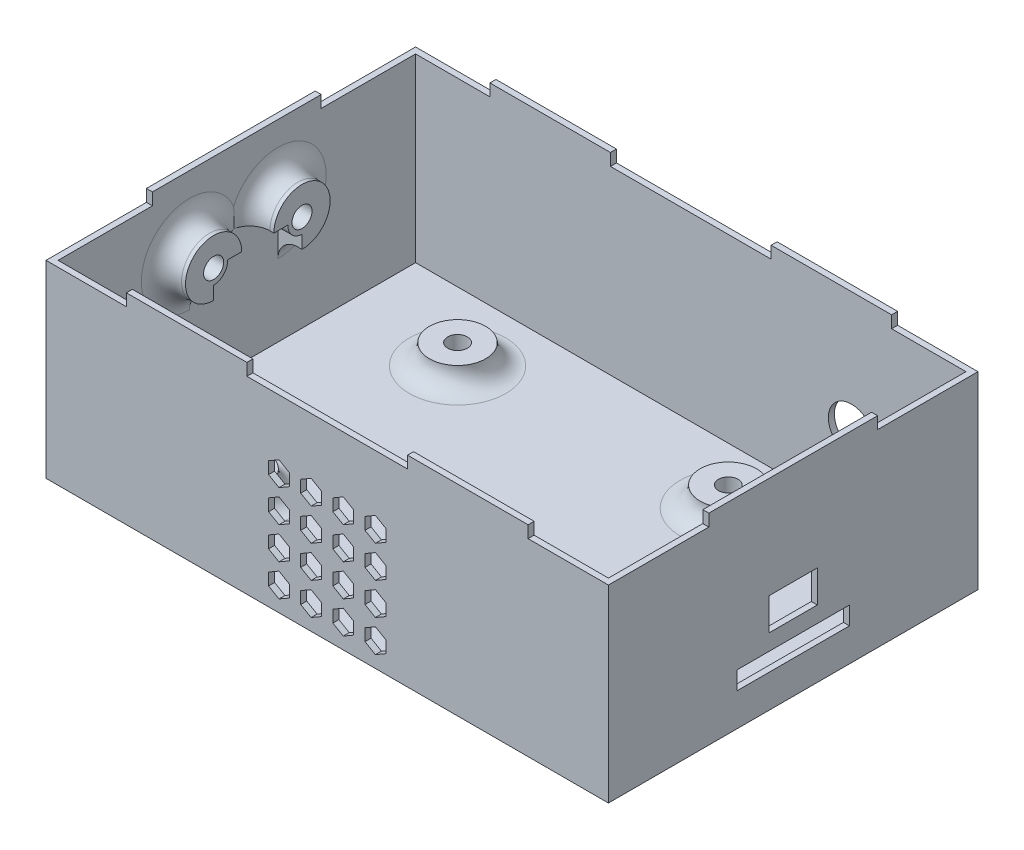
SolidWorks part; units mm, degrees
ref_plane "Front Plane" through (0, 0, 0) normal (0, 0, 1) x (1, 0, 0)
ref_plane "Top Plane" through (0, 0, 0) normal (0, 1, 0) x (1, 0, 0)
ref_plane "Right Plane" through (0, 0, 0) normal (1, 0, 0) x (0, 0, -1)
sketch "Sketch1" plane through (0, 0, 0) normal (0, 1, 0) x (1, 0, 0)
  line L1 (70, -46) -> (-70, -46)
  line L2 (70, -46) -> (70, 46)
  line L3 (70, 46) -> (-70, 46)
  line L4 (-70, -46) -> (-70, 46)
  line L5 (70, -46) -> (-70, 46) construction
  line L6 (70, 46) -> (-70, -46) construction
  line L12 (38, 12.25) -> (80, 12.25)
  line L13 (38, 12.25) -> (38, -12.25)
  line L14 (38, -12.25) -> (80, -12.25)
  line L15 (80, 12.25) -> (80, -12.25)
  line L16 (38, 12.25) -> (80, -12.25) construction
  line L17 (38, -12.25) -> (80, 12.25) construction
  line L22 (68.5, -44.5) -> (-68.5, -44.5)
  line L23 (68.5, -44.5) -> (68.5, 44.5)
  line L24 (68.5, 44.5) -> (-68.5, 44.5)
  line L25 (-68.5, -44.5) -> (-68.5, 44.5)
  line L26 (68.5, -44.5) -> (-68.5, 44.5) construction
  line L27 (68.5, 44.5) -> (-68.5, -44.5) construction
  circle A0 centre (-41.0549, 27.5) radius 7
  circle A1 centre (-41.0549, -27) radius 7
  circle A2 centre (23.3451, 30.5) radius 7
  circle A6 centre (40, -10.25) radius 3.5
  circle A7 centre (40, 10.25) radius 3.5
  point P0 (0, 0)
  point P6 (0, 0)
  point P9 (0, 0)
  point P22 (59, 0)
  dimension "D7" = 14
  dimension "D8" = 14
  dimension "D5" = 3
  dimension "D11" = 14
  dimension "D25" = 7
  dimension "D27" = 7
  dimension "D13" = 35.75
  dimension "D9" = 17
  dimension "D1" = 140
  dimension "D3" = 64.4
  dimension "D4" = 54.5
  dimension "D6" = 0
  dimension "D10" = 92
  dimension "D12" = 1.5
  dimension "D14" = 28.9451
  dimension "D19" = 30
  dimension "D20" = 20.5
  dimension "D21" = 10
  dimension "D23" = 2
  dimension "D24" = 1.5
  dimension "D26" = 2
  dimension "D28" = 2
  dimension "D29" = 30
extrude "Boss-Extrude2" add sketch "Sketch1" along normal blind 7 contours A2 | A0 | A1 | A6 | A7 region at (-41.0549, 0, -27.5) region at (-41.0549, 0, 27) region at (23.3451, 0, -30.5)
sketch "Sketch3" plane through (0, 0, 0) normal (0, 1, 0) x (1, 0, 0)
  line L1 (-70, -46) -> (70, -46)
  line L2 (-70, -46) -> (-70, 46)
  line L3 (-70, 46) -> (70, 46)
  line L4 (70, -46) -> (70, 46)
  line L5 (-70, -46) -> (70, 46) construction
  line L6 (-70, 46) -> (70, -46) construction
  point P0 (0, 0)
  dimension "D1" = 92
  dimension "D2" = 140
extrude "Boss-Extrude3" add sketch "Sketch3" along normal blind 2
sketch "Sketch4" plane through (0, 2, 0) normal (0, 1, 0) x (1, 0, 0)
  line L0 (70, 46) -> (-70, 46) construction
  line L1 (68.5, -44.5) -> (-68.5, -44.5)
  line L2 (68.5, -44.5) -> (68.5, 44.5)
  line L3 (68.5, 44.5) -> (-68.5, 44.5)
  line L4 (-68.5, -44.5) -> (-68.5, 44.5)
  line L5 (68.5, -44.5) -> (-68.5, 44.5) construction
  line L6 (68.5, 44.5) -> (-68.5, -44.5) construction
  line L7 (-70, 46) -> (-70, -46) construction
  line L9 (70, -46) -> (-70, -46)
  line L10 (70, -46) -> (70, 46)
  line L11 (70, 46) -> (-70, 46)
  line L12 (-70, -46) -> (-70, 46)
  line L13 (70, -46) -> (-70, 46) construction
  line L14 (70, 46) -> (-70, -46) construction
  point P0 (0, 0)
  point P10 (0, 0)
  dimension "D1" = 1.5
  dimension "D2" = 1.5
extrude "Boss-Extrude4" add sketch "Sketch4" along normal blind 45
sketch "Sketch5" plane through (0, 7, 0) normal (0, 1, 0) x (1, 0, 0)
  circle A0 centre (23.3451, 30.5) radius 2.45
  circle A1 centre (-41.0549, 27.5) radius 2.45
  circle A2 centre (-41.0549, -27) radius 2.45
  dimension "D1" = 4.9
  dimension "D4" = 4.9
  dimension "D5" = 4.9
extrude "Cut-Extrude1" cut sketch "Sketch5" against normal blind 5.1
sketch "Sketch6" plane through (0, 7, 0) normal (0, 1, 0) x (1, 0, 0)
  circle A0 centre (40, 10.25) radius 1
  circle A1 centre (40, -10.25) radius 1
  dimension "D1" = 2
  dimension "D2" = 2
extrude "Cut-Extrude2" cut sketch "Sketch6" against normal blind 5.1
sketch "Sketch7" plane through (-68.5, 0, 0) normal (1, 0, 0) x (0, 0, -1)
  line L0 (44.5, 2) -> (-44.5, 2) construction
  circle A0 centre (-11.7728, 32) radius 7
  circle A1 centre (10.2272, 32) radius 7
  dimension "D2" = 14
  dimension "D3" = 14
  dimension "D1" = 22
  dimension "D4" = 30
extrude "Boss-Extrude5" add sketch "Sketch7" along normal blind 6
sketch "Sketch8" plane through (-62.5, 0, 0) normal (1, 0, 0) x (0, 0, -1)
  circle A0 centre (-11.7728, 32) radius 2.5
  circle A1 centre (10.2272, 32) radius 2.5
  dimension "D1" = 5
  dimension "D2" = 5
extrude "Cut-Extrude3" cut sketch "Sketch8" against normal blind 5.1
sketch "Sketch9" plane through (0, 47, 0) normal (0, 1, 0) x (1, 0, 0)
  line L0 (-68.5, -44.5) -> (68.5, -44.5) construction
  line L1 (-50, -44.5) -> (-20, -44.5)
  line L2 (-50, -44.5) -> (-50, -46)
  line L3 (-50, -46) -> (-20, -46)
  line L4 (-20, -44.5) -> (-20, -46)
  line L5 (-70, -46) -> (70, -46) construction
  line L6 (-68.5, -44.5) -> (68.5, -44.5) construction
  line L7 (20, -44.5) -> (50, -44.5)
  line L8 (20, -44.5) -> (20, -46)
  line L9 (20, -46) -> (50, -46)
  line L10 (50, -44.5) -> (50, -46)
  line L11 (-70, 46) -> (-70, -46) construction
  line L12 (70, -46) -> (70, 46) construction
  line L13 (68.5, -44.5) -> (68.5, 44.5) construction
  line L18 (68.5, 21) -> (70, 21)
  line L19 (68.5, 21) -> (68.5, -21)
  line L20 (68.5, -21) -> (70, -21)
  line L21 (-68.5, 44.5) -> (-68.5, -44.5) construction
  line L22 (-68.5, -21) -> (-70, -21)
  line L23 (-68.5, -21) -> (-68.5, 21)
  line L24 (-68.5, 21) -> (-70, 21)
  line L25 (-70, -21) -> (-70, 21)
  line L26 (70, 46) -> (-70, 46) construction
  line L27 (70, 21) -> (70, -21)
  line L28 (68.5, 44.5) -> (-68.5, 44.5) construction
  line L29 (20, 44.5) -> (50, 44.5)
  line L30 (20, 44.5) -> (20, 46)
  line L31 (20, 46) -> (50, 46)
  line L32 (50, 44.5) -> (50, 46)
  line L34 (-50, 44.5) -> (-20, 44.5)
  line L35 (-50, 44.5) -> (-50, 46)
  line L36 (-50, 46) -> (-20, 46)
  line L37 (-20, 44.5) -> (-20, 46)
  dimension "D1" = 20
  dimension "D2" = 20
  dimension "D3" = 30
  dimension "D4" = 30
  dimension "D5" = 25
  dimension "D6" = 25
  dimension "D7" = 20
  dimension "D8" = 20
  dimension "D9" = 30
  dimension "D10" = 30
  dimension "D11" = 25
  dimension "D12" = 25
extrude "Boss-Extrude6" add sketch "Sketch9" along normal blind 3
sketch "Sketch11" plane through (70, 0, 0) normal (1, 0, 0) x (0, 0, -1)
  line L0 (-46, 0) -> (46, 0) construction
  line L1 (-14, 8.2) -> (14, 8.2)
  line L2 (-14, 8.2) -> (-14, 12.7)
  line L3 (-14, 12.7) -> (14, 12.7)
  line L4 (14, 8.2) -> (14, 12.7)
  line L5 (-46, 47) -> (-46, 0) construction
  line L7 (46, 47) -> (46, 0) construction
  dimension "D1" = 8.2
  dimension "D2" = 32
  dimension "D3" = 32
  dimension "D4" = 4.5
sketch "Sketch12" plane through (0, 7, 0) normal (0, 1, 0) x (1, 0, 0)
  circle A0 centre (40, 10.25) radius 3.5
  circle A1 centre (40, -10.25) radius 3.5
  circle A2 centre (40, 10.25) radius 1
  circle A3 centre (40, -10.25) radius 1
  dimension "D1" = 2
  dimension "D2" = 7
  dimension "D3" = 2
  dimension "D4" = 7
extrude "Boss-Extrude7" add sketch "Sketch12" along normal blind 2
extrude "Cut-Extrude4" cut sketch "Sketch11" against normal up to next
sketch "Sketch14" plane through (0, 0, -46) normal (0, 0, -1) x (-1, 0, 0)
  line L0 (-70, 47) -> (-70, 0) construction
  line L1 (-70, 0) -> (70, 0) construction
  circle A0 centre (-40, 20) radius 5.75
  dimension "D1" = 30
  dimension "D3" = 11.5
  dimension "D2" = 20
extrude "Cut-Extrude5" cut sketch "Sketch14" against normal up to next
sketch "Sketch15" plane through (0, 0, 46) normal (0, 0, 1) x (1, 0, 0)
  line L98 (-4.0006, 9) -> (-6.5987, 7.5)
  line L297 (-12.0019, 9) -> (-14.6, 7.5)
  line L299 (-14.6, 7.5) -> (-14.6, 4.5)
  line L301 (-14.6, 4.5) -> (-12.0019, 3)
  line L302 (-12.0019, 3) -> (-9.4038, 4.5)
  line L307 (-9.4038, 4.5) -> (-9.4038, 7.5)
  line L308 (-9.4038, 7.5) -> (-12.0019, 9)
  line L309 (-6.5987, 7.5) -> (-6.5987, 4.5)
  line L310 (-6.5987, 4.5) -> (-4.0006, 3)
  line L311 (-4.0006, 3) -> (-1.4026, 4.5)
  line L312 (-1.4026, 4.5) -> (-1.4026, 7.5)
  line L313 (-1.4026, 7.5) -> (-4.0006, 9)
  line L314 (4.0006, 9) -> (1.4026, 7.5)
  line L315 (1.4026, 7.5) -> (1.4026, 4.5)
  line L316 (1.4026, 4.5) -> (4.0006, 3)
  line L317 (4.0006, 3) -> (6.5987, 4.5)
  line L318 (6.5987, 4.5) -> (6.5987, 7.5)
  line L319 (6.5987, 7.5) -> (4.0006, 9)
  line L320 (12.0019, 9) -> (9.4038, 7.5)
  line L321 (9.4038, 7.5) -> (9.4038, 4.5)
  line L322 (9.4038, 4.5) -> (12.0019, 3)
  line L323 (12.0019, 3) -> (14.6, 4.5)
  line L324 (14.6, 4.5) -> (14.6, 7.5)
  line L325 (14.6, 7.5) -> (12.0019, 9)
  line L326 (-4.0006, 17) -> (-6.5987, 15.5)
  line L327 (-6.5987, 15.5) -> (-6.5987, 12.5)
  line L328 (-6.5987, 12.5) -> (-4.0006, 11)
  line L329 (-4.0006, 11) -> (-1.4026, 12.5)
  line L330 (-1.4026, 12.5) -> (-1.4026, 15.5)
  line L331 (-1.4026, 15.5) -> (-4.0006, 17)
  line L332 (4.0007, 17) -> (1.4026, 15.5)
  line L333 (1.4026, 15.5) -> (1.4026, 12.5)
  line L334 (1.4026, 12.5) -> (4.0007, 11)
  line L335 (4.0007, 11) -> (6.5987, 12.5)
  line L336 (6.5987, 12.5) -> (6.5987, 15.5)
  line L337 (6.5987, 15.5) -> (4.0007, 17)
  line L338 (12.0019, 17) -> (9.4039, 15.5)
  line L339 (9.4039, 15.5) -> (9.4039, 12.5)
  line L340 (9.4039, 12.5) -> (12.0019, 11)
  line L341 (12.0019, 11) -> (14.6, 12.5)
  line L342 (14.6, 12.5) -> (14.6, 15.5)
  line L343 (14.6, 15.5) -> (12.0019, 17)
  line L344 (-4.0006, 25) -> (-6.5987, 23.5)
  line L345 (-6.5987, 23.5) -> (-6.5987, 20.5)
  line L346 (-6.5987, 20.5) -> (-4.0006, 19)
  line L347 (-4.0006, 19) -> (-1.4025, 20.5)
  line L348 (-1.4025, 20.5) -> (-1.4025, 23.5)
  line L349 (-1.4025, 23.5) -> (-4.0006, 25)
  line L350 (4.0007, 25) -> (1.4026, 23.5)
  line L351 (1.4026, 23.5) -> (1.4026, 20.5)
  line L352 (1.4026, 20.5) -> (4.0007, 19)
  line L353 (4.0007, 19) -> (6.5987, 20.5)
  line L354 (6.5987, 20.5) -> (6.5987, 23.5)
  line L355 (6.5987, 23.5) -> (4.0007, 25)
  line L356 (12.0019, 25) -> (9.4039, 23.5)
  line L357 (9.4039, 23.5) -> (9.4039, 20.5)
  line L358 (9.4039, 20.5) -> (12.0019, 19)
  line L359 (12.0019, 19) -> (14.6, 20.5)
  line L360 (14.6, 20.5) -> (14.6, 23.5)
  line L361 (14.6, 23.5) -> (12.0019, 25)
  line L362 (-4.0006, 33) -> (-6.5987, 31.5)
  line L363 (-6.5987, 31.5) -> (-6.5987, 28.5)
  line L364 (-6.5987, 28.5) -> (-4.0006, 27)
  line L365 (-4.0006, 27) -> (-1.4025, 28.5)
  line L366 (-1.4025, 28.5) -> (-1.4025, 31.5)
  line L367 (-1.4025, 31.5) -> (-4.0006, 33)
  line L368 (4.0007, 33) -> (1.4026, 31.5)
  line L369 (1.4026, 31.5) -> (1.4026, 28.5)
  line L370 (1.4026, 28.5) -> (4.0007, 27)
  line L371 (4.0007, 27) -> (6.5987, 28.5)
  line L372 (6.5987, 28.5) -> (6.5987, 31.5)
  line L373 (6.5987, 31.5) -> (4.0007, 33)
  line L374 (12.002, 33) -> (9.4039, 31.5)
  line L375 (9.4039, 31.5) -> (9.4039, 28.5)
  line L376 (9.4039, 28.5) -> (12.002, 27)
  line L377 (12.002, 27) -> (14.6, 28.5)
  line L378 (14.6, 28.5) -> (14.6, 31.5)
  line L379 (14.6, 31.5) -> (12.002, 33)
  line L380 (-12.0019, 17) -> (-14.6, 15.5)
  line L381 (-14.6, 15.5) -> (-14.6, 12.5)
  line L382 (-14.6, 12.5) -> (-12.0019, 11)
  line L383 (-12.0019, 11) -> (-9.4038, 12.5)
  line L384 (-9.4038, 12.5) -> (-9.4038, 15.5)
  line L385 (-9.4038, 15.5) -> (-12.0019, 17)
  line L386 (-12.0019, 25) -> (-14.6, 23.5)
  line L387 (-14.6, 23.5) -> (-14.6, 20.5)
  line L388 (-14.6, 20.5) -> (-12.0019, 19)
  line L389 (-12.0019, 19) -> (-9.4038, 20.5)
  line L390 (-9.4038, 20.5) -> (-9.4038, 23.5)
  line L391 (-9.4038, 23.5) -> (-12.0019, 25)
  line L392 (-12.0019, 33) -> (-14.6, 31.5)
  line L393 (-14.6, 31.5) -> (-14.6, 28.5)
  line L394 (-14.6, 28.5) -> (-12.0019, 27)
  line L395 (-12.0019, 27) -> (-9.4038, 28.5)
  line L396 (-9.4038, 28.5) -> (-9.4038, 31.5)
  line L397 (-9.4038, 31.5) -> (-12.0019, 33)
  line L398 (-70, 47) -> (-70, 0) construction
  line L401 (-70, 0) -> (70, 0) construction
  circle A4 centre (-12.0019, 6) radius 2.5981 construction
  dimension "D3" = 55.4
  dimension "D4" = 6
  dimension "D7" = 8.0013
  dimension "D1" = 4
  dimension "D2" = 4
extrude "Cut-Extrude7" cut sketch "Sketch15" against normal up to next
fillet "Fillet1" radius 5 7 edges at (-41.0549, 2, 20) (40, 2, -13.75) (40, 2, 6.75) (-41.0549, 2, -34.5) (-68.5, 32, 4.7728) (-68.5, 32, -17.2272) (23.3451, 2, -37.5)
sketch "Sketch16" plane through (-62.5, 0, 0) normal (1, 0, 0) x (0, 0, -1)
  line L8 (-8.2728, 32) -> (6.7272, 32)
  line L11 (-11.7728, 18.25) -> (10.2272, 18.25)
  line L13 (-11.7728, 28.25) -> (-11.7728, 18.25)
  line L14 (10.2272, 28.25) -> (10.2272, 18.25)
  arc A10 (-11.7728, 28.25) -> (-8.2728, 32) centre (-11.8978, 31.875) ccw
  arc A11 (6.7272, 32) -> (10.2272, 28.25) centre (10.3522, 31.875) ccw
extrude "Cut-Extrude8" cut sketch "Sketch16" against normal up to surface (6 mm away) contours A11 L14 L11 L13 A10 L8 up to face at (-68.5, 32, -0.5268)
sketch "Sketch17" plane through (70, 0, 0) normal (1, 0, 0) x (0, 0, -1)
  line L0 (14, 12.7) -> (-14, 12.7) construction
  line L1 (6, 16.7) -> (-6, 16.7)
  line L2 (6, 16.7) -> (6, 24.7)
  line L3 (6, 24.7) -> (-6, 24.7)
  line L4 (-6, 16.7) -> (-6, 24.7)
  line L5 (6, 16.7) -> (-6, 24.7) construction
  line L6 (6, 24.7) -> (-6, 16.7) construction
  line L8 (-46, 47) -> (-46, 0) construction
  line L9 (46, 47) -> (46, 0) construction
  point P0 (0, 20.7)
  dimension "D1" = 4
  dimension "D2" = 40
  dimension "D3" = 40
  dimension "D4" = 8
extrude "Cut-Extrude9" cut sketch "Sketch17" against normal up to next
